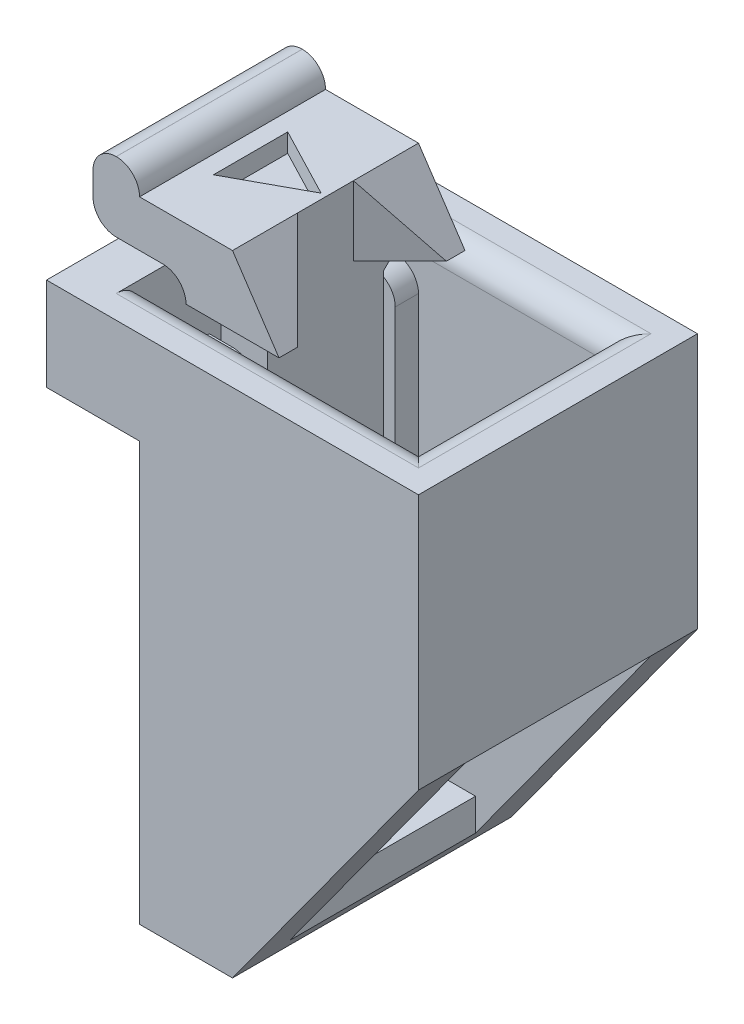
SolidWorks part; units mm, degrees
ref_plane "Front Plane" through (0, 0, 0) normal (0, 0, 1) x (1, 0, 0)
ref_plane "Top Plane" through (0, 0, 0) normal (0, 1, 0) x (1, 0, 0)
ref_plane "Right Plane" through (0, 0, 0) normal (1, 0, 0) x (0, 0, -1)
sketch "BaseSketch" plane through (0, 0, 0) normal (0, 1, 0) x (1, 0, 0)
  line L1 (-6.2677, 3.9685) -> (9.7323, 3.9685)
  line L2 (-6.2677, 3.9685) -> (-6.2677, -8.0315)
  line L3 (-6.2677, -8.0315) -> (9.7323, -8.0315)
  line L4 (9.7323, 3.9685) -> (9.7323, -8.0315)
  dimension "D1" = 16
  dimension "D2" = 12
extrude "BaseExtrude" add sketch "BaseSketch" along normal blind 2
sketch "SlotSketch" plane through (0, 2, 0) normal (0, 1, 0) x (1, 0, 0)
  line L10 (-2.2677, 0.9685) -> (-0.2677, 0.9685)
  line L11 (-2.2677, 1.9685) -> (-4.2677, 1.9685)
  line L12 (-2.2677, 1.9685) -> (-2.2677, 0.9685)
  line L13 (-0.2677, -6.0315) -> (7.7323, -6.0315)
  line L14 (7.7323, -6.0315) -> (7.7323, 1.9685)
  line L15 (-4.2677, -6.0315) -> (7.7323, -6.0315)
  line L16 (-4.2677, 1.9685) -> (-4.2677, -6.0315)
  line L17 (7.7323, 1.9685) -> (-4.2677, 1.9685)
  line L18 (7.7323, -6.0315) -> (7.7323, 1.9685)
  line L19 (-4.2677, -6.0315) -> (-2.2677, -6.0315)
  line L20 (-4.2677, 1.9685) -> (-4.2677, -6.0315)
  line L21 (7.7323, 1.9685) -> (-0.2677, 1.9685)
  line L22 (-0.2677, 1.9685) -> (-0.2677, 0.9685)
  line L23 (-2.2677, -5.0315) -> (-0.2677, -5.0315)
  line L24 (-2.2677, 0.4685) -> (-2.2677, -4.5315)
  line L25 (-2.2677, 0.4685) -> (-0.2677, 0.4685)
  line L26 (-2.2677, 0.4685) -> (-2.2677, -4.5315)
  line L27 (-2.2677, -4.5315) -> (-0.2677, -4.5315)
  line L28 (-0.2677, 0.4685) -> (-0.2677, -4.5315)
  line L29 (-0.2677, 0.4685) -> (-0.2677, -4.5315)
  line L30 (-2.2677, -5.0315) -> (-2.2677, -6.0315)
  line L31 (-0.2677, -5.0315) -> (-0.2677, -6.0315)
  line L33 (-6.2677, 3.9685) -> (9.7323, 3.9685)
  line L34 (-6.2677, 3.9685) -> (-6.2677, -8.0315)
  line L35 (-6.2677, -8.0315) -> (9.7323, -8.0315)
  line L36 (9.7323, 3.9685) -> (9.7323, -8.0315)
  line M5 (-6.2677, 3.9685) -> (-6.2677, -8.0315)
  line M6 (-6.2677, -8.0315) -> (9.7323, -8.0315)
  line M7 (9.7323, -8.0315) -> (9.7323, 3.9685)
  line M8 (9.7323, 3.9685) -> (-6.2677, 3.9685)
  dimension "D2" = 8
  dimension "D3" = 2
  dimension "D4" = 2
  dimension "D5" = 8
  dimension "D6" = 1
  dimension "D7" = 1
  dimension "D8" = 5
  dimension "D9" = 0.5
  dimension "D1" = 2
extrude "FlapExtrude" add sketch "SlotSketch" along normal blind 20.1 contours L25 L28 L27 L24
sketch "HandleBaseSketch" plane through (0, 22.1, 0) normal (0, 1, 0) x (1, 0, 0)
  line L0 (9.7323, 3.9685) -> (-6.2677, 3.9685) construction
  line L1 (-2.2677, 1.9685) -> (-0.2677, 1.9685)
  line L2 (-2.2677, 1.9685) -> (-2.2677, -6.0315)
  line L3 (-2.2677, -6.0315) -> (-0.2677, -6.0315)
  line L4 (-0.2677, 1.9685) -> (-0.2677, -6.0315)
  line L5 (-6.2677, -8.0315) -> (9.7323, -8.0315) construction
  dimension "D1" = 2
  dimension "D2" = 2
extrude "HandleBase" add sketch "HandleBaseSketch" along normal blind 3
sketch "TriangleBaseSketch" plane through (-0.2677, 0, 0) normal (1, 0, 0) x (0, 0, -1)
  line L0 (-6.0315, 22.1) -> (-3.2315, 22.1)
  line L1 (-3.2315, 22.1) -> (-3.2315, 25.1)
  line L2 (-6.0315, 25.1) -> (1.9685, 25.1) construction
  line L3 (-3.2315, 25.1) -> (-6.0315, 25.1)
  line L4 (-6.0315, 25.1) -> (-6.0315, 22.1)
  line L5 (1.9685, 22.1) -> (-0.8315, 22.1)
  line L6 (-0.8315, 22.1) -> (-0.8315, 25.1)
  line L7 (-0.8315, 25.1) -> (1.9685, 25.1)
  line L8 (1.9685, 25.1) -> (1.9685, 22.1)
extrude "PyramidExtrude" add sketch "TriangleBaseSketch" along normal blind 2.8
sketch "PyramidSideCutSketch" plane through (0, 0, -1.9685) normal (0, 0, -1) x (-1, 0, 0)
  line L0 (0.2677, 25.1) -> (0.2677, 22.1)
  line L1 (0.2677, 25.1) -> (-2.5323, 25.1)
  line L2 (-2.5323, 25.1) -> (-2.5323, 22.1)
  line L3 (-2.5323, 22.1) -> (-1.7323, 22.1)
  line L4 (-2.5323, 22.1) -> (2.2677, 22.1) construction
  line L5 (-1.7323, 22.1) -> (0.2677, 25.1)
  dimension "D1" = 2
sketch "PyramidTopCutSketch" plane through (0, 25.1, 0) normal (0, 1, 0) x (1, 0, 0)
  line L0 (-0.2677, -3.2315) -> (2.5323, -6.0315)
  line L1 (2.5323, -6.0315) -> (2.5323, -3.2315)
  line L2 (2.5323, -3.2315) -> (-0.2677, -3.2315)
  line L3 (-0.2677, -0.8315) -> (2.5323, 1.9685)
  line L4 (2.5323, 1.9685) -> (2.5323, -0.8315)
  line L5 (2.5323, -0.8315) -> (-0.2677, -0.8315)
extrude "PyramidTopCut" cut sketch "PyramidTopCutSketch" against normal blind 3
extrude "PyramidSideCut" cut sketch "PyramidSideCutSketch" against normal through all contours L1 L2 L3 L5
extrude "Boss-Extrude5" add sketch "SlotSketch<6>" along normal blind 3 contours L31 L23 L30 L19 L20 L11 L12 L10 L22 L21 L18 L13 M8 M5 M6 M7 | L12 L10 L22 L21 L18 L13 L31 L23 L30 L19 L20 L11 | L33 L36 L35 L34 region at (-1.2677, 2, -1.4685) region at (-1.2677, 2, 5.5315) region at (1.7323, 2, -3.7685)
sketch "SlotSketch<6>" plane through (0, 2, 0) normal (0, 1, 0) x (1, 0, 0) same geometry as "SlotSketch"
extrude "Sides" add sketch "SlotSketch<7>" along normal blind 20 contours L11 L20 L19 L30 L23 L31 L13 L18 L21 L22 L10 L12 | L33 L36 L35 L34
sketch "SlotSketch<7>" plane through (0, 2, 0) normal (0, 1, 0) x (1, 0, 0) same geometry as "SlotSketch"
sketch "Sketch7" plane through (-0.2677, 0, 0) normal (1, 0, 0) x (0, 0, -1)
  line L0 (-5.0315, 22) -> (-5.0315, 2) construction
  line L1 (-6.0315, 22) -> (-5.0315, 22)
  line L2 (-6.0315, 22) -> (-6.0315, 20.4974)
  line L3 (-6.0315, 20.4974) -> (-5.0315, 20.4974)
  line L4 (-5.0315, 22) -> (-5.0315, 20.4974)
  line L5 (1.9685, 22) -> (1.9685, 2) construction
  line L6 (0.9685, 22) -> (1.9685, 22)
  line L7 (0.9685, 22) -> (0.9685, 20.4974)
  line L8 (0.9685, 20.4974) -> (1.9685, 20.4974)
  line L9 (1.9685, 22) -> (1.9685, 20.4974)
extrude "WallClearanceCut" cut sketch "Sketch7" against normal blind 2
sketch "BaseTriangleCutSketch" plane through (0, 0, 8.0315) normal (0, 0, 1) x (1, 0, 0)
  line L0 (9.7323, 0) -> (1.7323, 0)
  line L1 (-6.2677, 0) -> (9.7323, 0) construction
  line L2 (1.7323, 0) -> (9.7323, 11)
  line L3 (9.7323, 22) -> (9.7323, 0) construction
  line L4 (9.7323, 11) -> (9.7323, 0)
extrude "BaseTriangleCut" cut sketch "BaseTriangleCutSketch" against normal through all
sketch "Sketch9" plane through (-2.2677, 0, 0) normal (-1, 0, 0) x (0, 0, 1)
  line L0 (6.0315, 25.1) -> (6.0315, 22.1) construction
  line L1 (-1.9685, 25.1) -> (6.0315, 25.1)
  line L2 (-1.9685, 25.1) -> (-1.9685, 23.1)
  line L3 (-1.9685, 23.1) -> (6.0315, 23.1)
  line L4 (6.0315, 25.1) -> (6.0315, 23.1)
extrude "Handle" add sketch "Sketch9" along normal blind 4
sketch "Sketch10" plane through (0, 25.1, 0) normal (0, 1, 0) x (1, 0, 0)
  line L0 (-0.2677, 1.9685) -> (-6.2677, 1.9685) construction
  line L1 (-6.2677, -6.0315) -> (-4.2659, -6.0315)
  line L2 (-6.2677, -6.0315) -> (-6.2677, 1.9685)
  line L3 (-6.2677, 1.9685) -> (-4.2659, 1.9685)
  line L4 (-4.2659, -6.0315) -> (-4.2659, 1.9685)
extrude "Boss-Extrude8" add sketch "Sketch10" along normal blind 1
sketch "WashHoleSketch" plane through (-6.2677, 0, 0) normal (-1, 0, 0) x (0, 0, 1)
  line L0 (-3.9685, 22) -> (-3.9685, 0) construction
  line L1 (-1.9685, 18) -> (6.0315, 18)
  line L2 (-1.9685, 18) -> (-1.9685, 4)
  line L3 (-1.9685, 4) -> (6.0315, 4)
  line L4 (6.0315, 18) -> (6.0315, 4)
  line L5 (8.0315, 22) -> (8.0315, 0) construction
  line L6 (-3.9685, 22) -> (8.0315, 22) construction
  line L7 (-3.9685, 0) -> (8.0315, 0) construction
  dimension "D1" = 2
  dimension "D2" = 2
  dimension "D3" = 4
  dimension "D4" = 4
extrude "WashHole" cut sketch "WashHoleSketch" against normal blind 2
fillet "Fillet1" radius 1 10 edges at (1.7323, 22, -1.9685) (1.7323, 22, 6.0315) (7.7323, 22, 2.0315) (-2.2677, 2, 2.0315) (-2.2677, 23.1, 2.0315) (-6.2677, 23.1, 2.0315) (-4.2659, 26.1, 2.0315) (-6.2677, 26.1, 2.0315) (-0.2677, 20.4974, -1.4685) (-0.2677, 20.4974, 5.5315)
sketch "MarkerSketch" plane through (0, 25.1, 0) normal (0, 1, 0) x (1, 0, 0)
  line L0 (-0.4994, -1.9893) -> (-3.4984, -0.4264)
  line L1 (-3.4984, -0.4264) -> (-3.4984, -3.6225)
  line L2 (-3.4984, -3.6225) -> (-0.4994, -1.9893)
extrude "Cut-Extrude6" cut sketch "MarkerSketch" against normal blind 0.8
sketch "Sketch11" plane through (7.7323, 0, 0) normal (-1, 0, 0) x (0, 0, 1)
  line L0 (-1.9685, 18) -> (-1.9685, 4) construction
  line L1 (-1.9685, 11) -> (6.0315, 11)
  line L2 (-1.9685, 11) -> (-1.9685, 8.25)
  line L3 (-1.9685, 8.25) -> (6.0315, 8.25)
  line L4 (6.0315, 11) -> (6.0315, 8.25)
extrude "Cut-Extrude7" cut sketch "Sketch11" against normal blind 10
sketch "Sketch12" plane through (0, 2, 0) normal (0, 1, 0) x (1, 0, 0)
  line L0 (-0.2677, -6.0315) -> (3.1868, -6.0315) construction
  line L1 (3.1868, 1.9685) -> (2.1868, 1.9685)
  line L2 (3.1868, 1.9685) -> (3.1868, -6.0315)
  line L3 (3.1868, -6.0315) -> (2.1868, -6.0315)
  line L4 (2.1868, 1.9685) -> (2.1868, -6.0315)
  dimension "D1" = 1
extrude "Cut-Extrude8" cut sketch "Sketch12" against normal blind 10
chamfer "Chamfer1" distance 1 angle 45 2 edges
sketch "Sketch14" plane through (0, 0, 8.0315) normal (0, 0, 1) x (1, 0, 0)
  line L0 (-6.2677, 0) -> (1.7323, 0) construction
  line L1 (-6.2677, 18) -> (-2.2677, 18)
  line L2 (-6.2677, 18) -> (-6.2677, 0)
  line L3 (-6.2677, 0) -> (-2.2677, 0)
  line L4 (-2.2677, 18) -> (-2.2677, 0)
extrude "Cut-Extrude9" cut sketch "Sketch14" against normal through all
